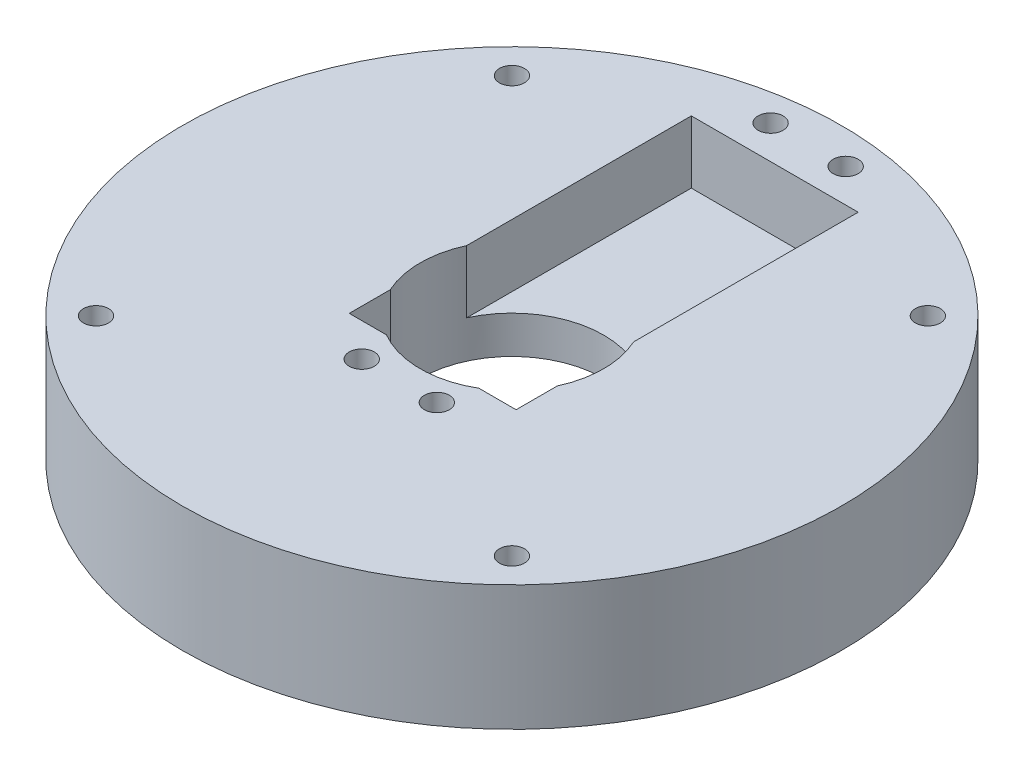
SolidWorks part; units mm, degrees
ref_plane "Alzado" through (0, 0, 0) normal (0, 0, 1) x (1, 0, 0)
ref_plane "Planta" through (0, 0, 0) normal (0, 1, 0) x (1, 0, 0)
ref_plane "Vista lateral" through (0, 0, 0) normal (1, 0, 0) x (0, 0, -1)
sketch "Croquis1" plane through (0, 0, 0) normal (0, 1, 0) x (1, 0, 0)
  line L0 (0, 0) -> (39.5, 0) construction
  line L1 (0, 0) -> (27.9307, 27.9307) construction
  circle A0 centre (0, 0) radius 39.5
  circle A1 centre (0, 0) radius 11
  circle A2 centre (24.9255, 24.9255) radius 1.5
  circle A3 centre (24.9255, -24.9255) radius 1.5
  circle A4 centre (-24.9255, -24.9255) radius 1.5
  circle A5 centre (-24.9255, 24.9255) radius 1.5
  point P17 (0, 0)
  dimension "D1" = 79
  dimension "D2" = 22
  dimension "D4" = 3
  dimension "D3" = 45
  dimension "D5" = 35.25
  dimension "D6" = 4
extrude "Saliente-Extruir2" add sketch "Croquis1" along normal blind 15
sketch "Croquis2" plane through (0, 15, 0) normal (0, 1, 0) x (1, 0, 0)
  line L0 (0, 0) -> (0, 39.5) construction
  line L1 (-4.5, 37.3505) -> (-4.5, -17.8193) construction
  line L2 (-10, -9.5) -> (10, -9.5)
  line L3 (-10, -9.5) -> (-10, 31.5)
  line L4 (-10, 31.5) -> (10, 31.5)
  line L5 (10, -9.5) -> (10, 31.5)
  line L6 (-10, -9.5) -> (10, 31.5) construction
  line L7 (-10, 31.5) -> (10, -9.5) construction
  line L8 (4.5, 37.3505) -> (4.5, -17.8193) construction
  line L9 (-4.5, -13.5) -> (4.5, -13.5) construction
  line L10 (-4.5, 35.5) -> (4.5, 35.5) construction
  circle A0 centre (0, 0) radius 39.5 construction
  circle A1 centre (-4.5, -13.5) radius 1.5
  circle A2 centre (4.5, -13.5) radius 1.5
  circle A3 centre (4.5, 35.5) radius 1.5
  circle A4 centre (-4.5, 35.5) radius 1.5
  point P6 (0, 11)
  dimension "D8" = 3
  dimension "D9" = 3
  dimension "D10" = 3
  dimension "D11" = 3
  dimension "D1" = 41
  dimension "D2" = 20
  dimension "D3" = 9.5
  dimension "D4" = 4
  dimension "D5" = 4
  dimension "D6" = 4.5
  dimension "D7" = 4.5
extrude "Cortar-Extruir1" cut sketch "Croquis2" against normal blind 7.5
extrude "Cortar-Extruir2" cut sketch "Croquis2<2>" against normal through all contours A4 | A3 | A2 | A1 region at (-4.5, 15, 13.5) region at (4.5, 15, 13.5) region at (4.5, 15, -35.5) region at (-4.5, 15, -35.5)
sketch "Croquis2<2>" plane through (0, 15, 0) normal (0, 1, 0) x (1, 0, 0) same geometry as "Croquis2"
sketch "Croquis3" plane through (0, 0, 0) normal (0, -1, 0) x (1, 0, 0)
  circle A0 centre (0, 0) radius 25
  dimension "D1" = 50
extrude "Cortar-Extruir3" cut sketch "Croquis3" against normal blind 3
